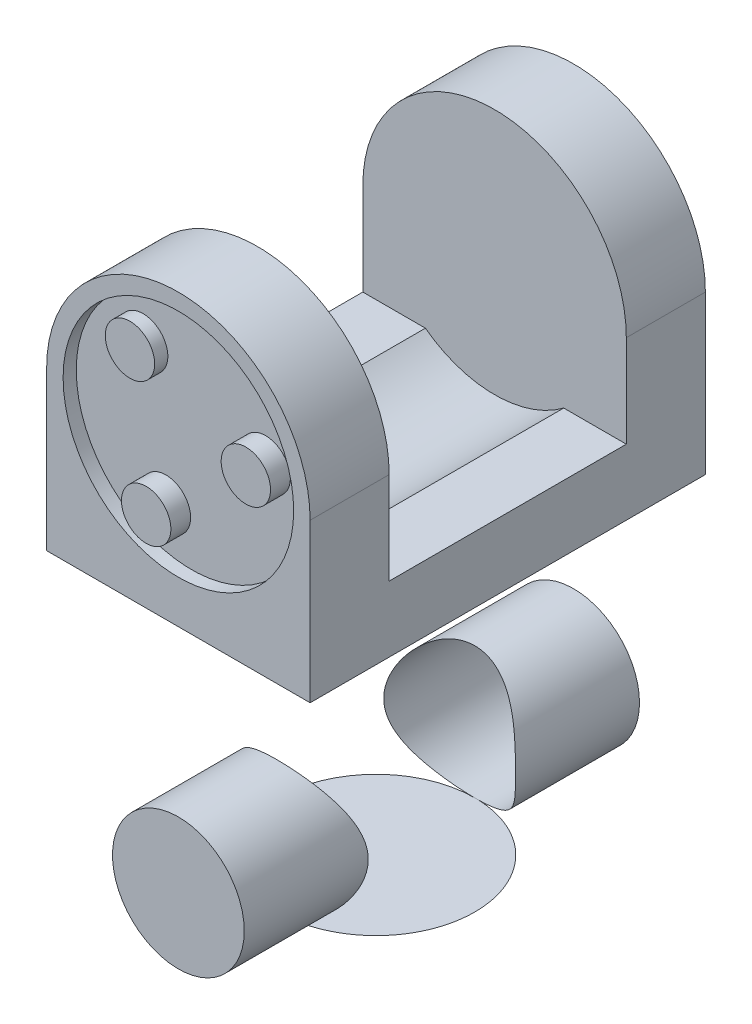
SolidWorks part; units mm, degrees
ref_plane "Front Plane" through (0, 0, 0) normal (0, 0, 1) x (1, 0, 0)
ref_plane "Top Plane" through (0, 0, 0) normal (0, 1, 0) x (1, 0, 0)
ref_plane "Right Plane" through (0, 0, 0) normal (1, 0, 0) x (0, 0, -1)
sketch "Sketch1" plane through (0, 0, 0) normal (0, 1, 0) x (1, 0, 0)
  circle A0 centre (0, 0) radius 38.1
  dimension "D1" = 76.2
extrude "Boss-Extrude1" add sketch "Sketch1" along normal blind 127
ref_plane "Plane1" through (0, 0, 76.2) normal (0, 0, 1) x (1, 0, 0)
sketch "Sketch3" plane through (0, 0, 76.2) normal (0, 0, 1) x (1, 0, 0)
  circle A0 centre (0, 38.1) radius 25.4
  dimension "D1" = 50.8
  dimension "D2" = 38.1
extrude "Boss-Extrude2" add sketch "Sketch3" against normal blind 152.4
sketch "Sketch4" plane through (0, 127, 0) normal (0, 1, 0) x (1, 0, 0)
  line L1 (50.8, -76.2) -> (-50.8, -76.2)
  line L2 (50.8, -76.2) -> (50.8, 76.2)
  line L3 (50.8, 76.2) -> (-50.8, 76.2)
  line L4 (-50.8, -76.2) -> (-50.8, 76.2)
  line L5 (0, 76.2) -> (0, -76.2) construction
  line L6 (50.8, 0) -> (-50.8, 0) construction
  point P0 (0, 0)
  dimension "D1" = 101.6
  dimension "D2" = 152.4
extrude "Boss-Extrude3" add sketch "Sketch4" along normal blind 10.16
sketch "Sketch5" plane through (0, 137.16, 0) normal (0, 1, 0) x (1, 0, 0)
  line L0 (-50.8, 76.2) -> (-50.8, -76.2) construction
  line L1 (50.8, 76.2) -> (-50.8, 76.2)
  line L2 (50.8, 76.2) -> (50.8, 45.72)
  line L3 (50.8, 45.72) -> (-50.8, 45.72)
  line L4 (-50.8, 76.2) -> (-50.8, 45.72)
  line L5 (0, 45.72) -> (0, 76.2) construction
  line L6 (50.8, 60.96) -> (-50.8, 60.96) construction
  line L7 (50.8, 76.2) -> (-50.8, 76.2) construction
  point P0 (0, 60.96)
  dimension "D1" = 30.48
  dimension "D2" = 60.96
extrude "Boss-Extrude4" add sketch "Sketch5" along normal blind 101.6
sketch "Sketch7" plane through (0, 0, -76.2) normal (0, 0, -1) x (-1, 0, 0)
  line L0 (-50.8, 238.76) -> (50.8, 238.76) construction
  line L1 (-50.8, 238.76) -> (-50.8, 127) construction
  line L2 (50.8, 238.76) -> (-50.8, 238.76)
  line L3 (50.8, 238.76) -> (50.8, 137.16)
  line L4 (50.8, 137.16) -> (-50.8, 137.16)
  line L5 (-50.8, 238.76) -> (-50.8, 137.16)
  line L6 (0, 137.16) -> (0, 238.76) construction
  line L7 (50.8, 187.96) -> (-50.8, 187.96) construction
  circle A0 centre (0, 187.96) radius 50.8
  line M8 (50.8, 238.76) -> (-50.8, 238.76)
  line M9 (-50.8, 238.76) -> (-50.8, 127)
  dimension "D1" = 101.6
extrude "Cut-Extrude1" cut sketch "Sketch7" against normal blind 101.6 contours A0 L2 M9 | A0 L3 M8 region at (-39.4529, 227.4129, -76.2) region at (39.4529, 227.4129, -76.2)
sketch "Sketch8" plane through (0, 0, -76.2) normal (0, 0, -1) x (-1, 0, 0)
  line L0 (44.45, 187.96) -> (50.8, 187.96) construction
  line L1 (-44.45, 187.96) -> (-50.8, 187.96) construction
  line L2 (-50.8, 187.96) -> (-44.45, 187.96)
  line L3 (-50.8, 187.96) -> (-50.8, 127)
  line L4 (-50.8, 127) -> (50.8, 127)
  line L5 (50.8, 127) -> (50.8, 187.96)
  line L6 (50.8, 187.96) -> (44.45, 187.96)
  circle A0 centre (0, 187.96) radius 44.45
  circle A1 centre (0, 187.96) radius 44.45
  circle A4 centre (18.669, 210.1535) radius 9.525
  circle A5 centre (0, 187.96) radius 44.45
  circle A6 centre (9.8857, 160.6954) radius 9.525
  circle A7 centre (0, 187.96) radius 44.45
  circle A8 centre (-28.5547, 193.0311) radius 9.525
  point P15 (0, 187.96)
  dimension "D1" = 88.9
  dimension "D2" = 19.05
  dimension "D3" = 18.669
  dimension "D4" = 3
extrude "Cut-Extrude3" cut sketch "Sketch8" against normal blind 5.08 contours A0 A8 A6 A4 region at (0, 187.96, -76.2)
extrude "Boss-Extrude6" add sketch "Sketch8<6>" along normal blind 2.54 contours A8 | A6 region at (-9.8857, 160.6954, -76.2) region at (28.5547, 193.0311, -76.2)
sketch "Sketch8<6>" plane through (0, 0, -76.2) normal (0, 0, -1) x (-1, 0, 0) same geometry as "Sketch8"
mirror "Mirror2" about plane through (0, 0, 0) normal (0, 0, 1) of "Cut-Extrude3", "Cut-Extrude1", "Boss-Extrude6", "Boss-Extrude4"
sketch "Sketch10" plane through (0, 0, -76.2) normal (0, 0, -1) x (-1, 0, 0)
  line L0 (-50.8, 152.4) -> (-26.67, 152.4)
  line L1 (26.67, 152.4) -> (50.8, 152.4)
  line L2 (50.8, 152.4) -> (50.8, 127)
  line L3 (50.8, 127) -> (-50.8, 127)
  line L4 (-50.8, 127) -> (-50.8, 152.4)
  line L5 (-50.8, 127) -> (50.8, 127) construction
  circle A1 centre (0, 187.96) radius 44.45 construction
  arc A2 (-26.67, 152.4) -> (26.67, 152.4) centre (0, 187.96) ccw
  dimension "D1" = 25.4
  dimension "D2" = 25.4
extrude "Boss-Extrude7" add sketch "Sketch10" against normal up to surface (121.92 mm away) up to face at (0, 175.26, 45.72)
sketch "Sketch11" plane through (0, 0, 0) normal (0, -1, 0) x (1, 0, 0)
  circle A0 centre (0, 0) radius 38.1
extrude "Cut-Extrude5" cut sketch "Sketch11" against normal blind 12.7
